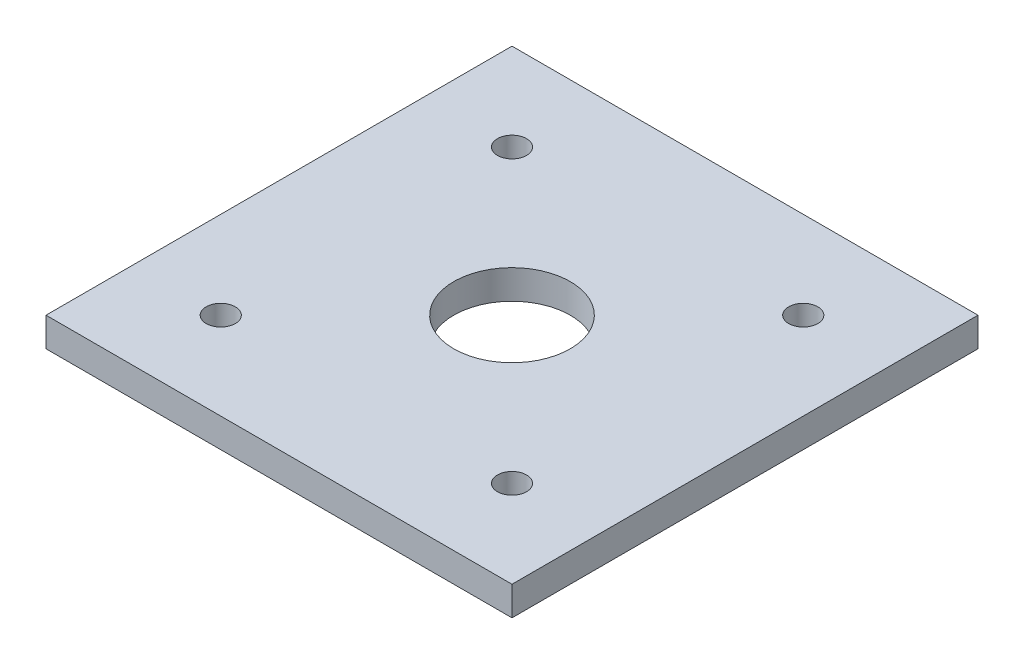
SolidWorks part; units mm, degrees
ref_plane "Front Plane" through (0, 0, 0) normal (0, 0, 1) x (1, 0, 0)
ref_plane "Top Plane" through (0, 0, 0) normal (0, 1, 0) x (1, 0, 0)
ref_plane "Right Plane" through (0, 0, 0) normal (1, 0, 0) x (0, 0, -1)
sketch "Sketch1" plane through (0, 0, 0) normal (0, 1, 0) x (1, 0, 0)
  line L1 (-50.8, 50.8) -> (50.8, 50.8)
  line L2 (-50.8, 50.8) -> (-50.8, -50.8)
  line L3 (-50.8, -50.8) -> (50.8, -50.8)
  line L4 (50.8, 50.8) -> (50.8, -50.8)
  line L5 (-50.8, 50.8) -> (50.8, -50.8) construction
  line L6 (-50.8, -50.8) -> (50.8, 50.8) construction
  circle A0 centre (0, 0) radius 12.7
  point P0 (0, 0)
  dimension "D2" = 25.4
  dimension "D1" = 101.6
extrude "Boss-Extrude1" add sketch "Sketch1" along normal blind 6.35
hole_wizard "1/4 (0.25) Diameter Hole1" positions "Sketch2" profile "Sketch3" hole size "1/4" standard "ANSI Inch" end condition through all
sketch "Sketch2" plane through (0, 6.35, 0) normal (0, 1, 0) x (1, 0, 0)
  line L0 (-50.8, 50.8) -> (-50.8, -50.8) construction
  line L1 (-50.8, -50.8) -> (50.8, -50.8) construction
  point P0 (-31.75, -31.75)
  dimension "D1" = 19.05
  dimension "D2" = 19.05
sketch "Sketch3" plane through (-31.75, 6.35, 31.75) normal (1, 0, 0) x (0, 0, 1)
  line L0 (0, 0) -> (0, 6.35)
  line L1 (0, 6.35) -> (3.175, 6.35)
  line L2 (3.175, 6.35) -> (3.175, 0)
  line L5 (3.175, 0) -> (0, 0)
  line L11 (0, -6.35) -> (0, 107.95) construction
  dimension "Thru Hole Dia." = 6.35
  dimension "Thru Hole Depth" = 6.35
pattern_circular "CirPattern1" count 4 over 360 about axis through (0, 6.35, 0) along (0, -1, 0) of "1/4 (0.25) Diameter Hole1" reverse direction yes
